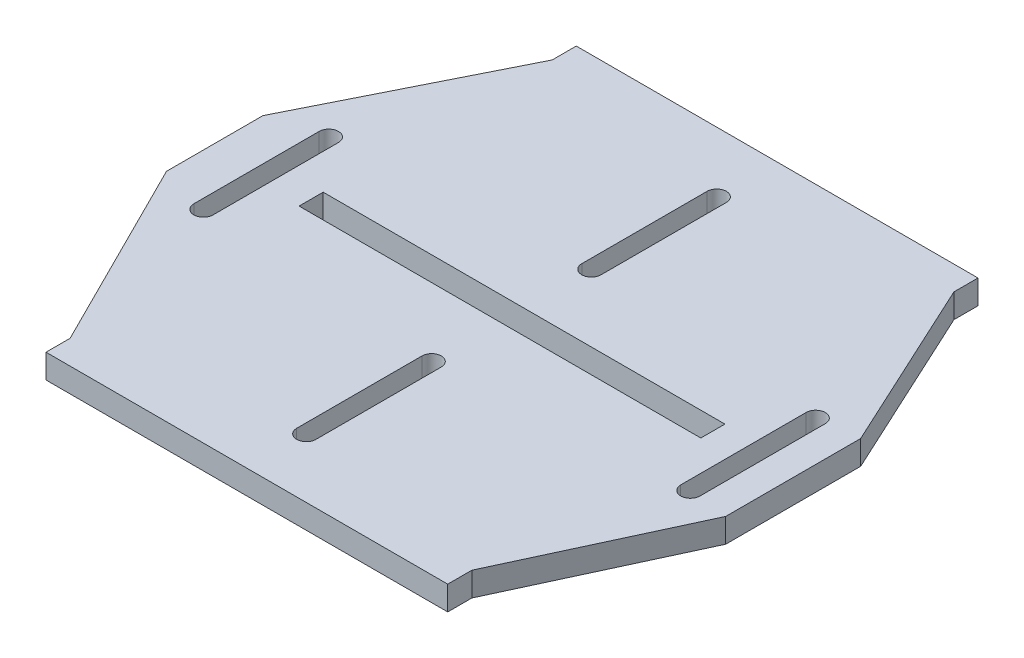
SolidWorks part; units mm, degrees
ref_plane "Front Plane" through (0, 0, 0) normal (0, 0, 1) x (1, 0, 0)
ref_plane "Top Plane" through (0, 0, 0) normal (0, 1, 0) x (1, 0, 0)
ref_plane "Right Plane" through (0, 0, 0) normal (1, 0, 0) x (0, 0, -1)
sketch "Sketch1" plane through (0, 0, 0) normal (0, 1, 0) x (1, 0, 0)
  line L8 (0, -7.5) -> (125, -7.5)
  line L10 (0, 157.5) -> (125, 157.5)
  line L12 (0, -7.5) -> (0, 0)
  line L14 (125, -7.5) -> (125, 0)
  line L15 (0, 157.5) -> (0, 150)
  line L16 (125, 157.5) -> (125, 150)
  line L17 (150, 54) -> (150, 96)
  line L18 (-30, 60) -> (-30, 90)
  line L19 (125, 150) -> (150, 96)
  line L20 (150, 54) -> (125, 0)
  line L21 (0, 0) -> (-30, 60)
  line L22 (-30, 90) -> (0, 150)
  line L23 (137.5, 55.5) -> (137.5, 94.5) construction
  line L24 (134.5, 55.5) -> (134.5, 94.5)
  line L25 (140.5, 55.5) -> (140.5, 94.5)
  line L26 (-14, 55.5) -> (-14, 94.5) construction
  line L27 (-17, 55.5) -> (-17, 94.5)
  line L28 (-11, 55.5) -> (-11, 94.5)
  line L29 (62.5, 11) -> (62.5, 50) construction
  line L30 (59.5, 11) -> (59.5, 50)
  line L31 (65.5, 11) -> (65.5, 50)
  line L32 (62.5, 138.7057) -> (62.5, 99.7057) construction
  line L33 (65.5, 138.7057) -> (65.5, 99.7057)
  line L34 (59.5, 138.7057) -> (59.5, 99.7057)
  line L36 (0, 78.75) -> (125, 78.75)
  line L37 (0, 78.75) -> (0, 71.25)
  line L38 (0, 71.25) -> (125, 71.25)
  line L39 (125, 78.75) -> (125, 71.25)
  arc A0 (134.5, 55.5) -> (140.5, 55.5) centre (137.5, 55.5) ccw
  arc A1 (140.5, 94.5) -> (134.5, 94.5) centre (137.5, 94.5) ccw
  arc A2 (-17, 55.5) -> (-11, 55.5) centre (-14, 55.5) ccw
  arc A3 (-11, 94.5) -> (-17, 94.5) centre (-14, 94.5) ccw
  arc A4 (59.5, 11) -> (65.5, 11) centre (62.5, 11) ccw
  arc A5 (65.5, 50) -> (59.5, 50) centre (62.5, 50) ccw
  arc A6 (65.5, 138.7057) -> (59.5, 138.7057) centre (62.5, 138.7057) ccw
  arc A7 (59.5, 99.7057) -> (65.5, 99.7057) centre (62.5, 99.7057) ccw
  point P18 (137.5, 75)
  point P23 (-14, 75)
  point P30 (62.5, 30.5)
  point P35 (62.5, 119.2057)
  point P36 (62.5, 78.75)
  point P37 (62.5, 157.5)
  point P38 (0, 75)
  point P39 (-30, 75)
  point P41 (0, 0)
  dimension "D2" = 7.5
  dimension "D3" = 125
extrude "Boss-Extrude6" add sketch "Sketch1" along normal blind 7.5
